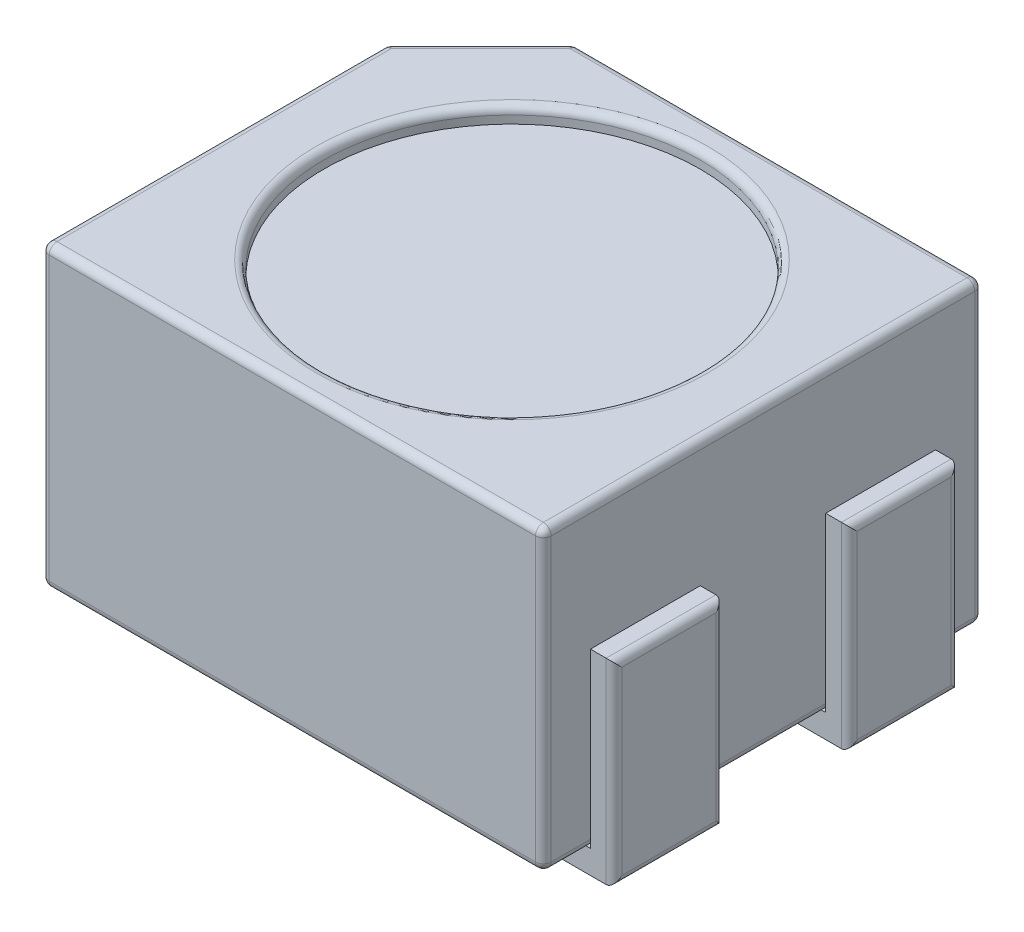
SolidWorks part; units mm, degrees
ref_plane "Спереди" through (0, 0, 0) normal (0, 0, 1) x (1, 0, 0)
ref_plane "Сверху" through (0, 0, 0) normal (0, 1, 0) x (1, 0, 0)
ref_plane "Справа" through (0, 0, 0) normal (1, 0, 0) x (0, 0, -1)
ref_plane "Плоскость1" through (0, 0.15, 0) normal (0, 1, 0) x (1, 0, 0)
sketch "Эскиз1" plane through (0, 0.15, 0) normal (0, 1, 0) x (1, 0, 0)
  line L1 (-1.6, -1.4) -> (1.6, -1.4)
  line L2 (-1.6, -1.4) -> (-1.6, 1.4)
  line L3 (-1.6, 1.4) -> (1.6, 1.4)
  line L4 (1.6, -1.4) -> (1.6, 1.4)
  line L5 (-1.6, -1.4) -> (1.6, 1.4) construction
  line L6 (-1.6, 1.4) -> (1.6, -1.4) construction
  point P0 (0, 0)
extrude "Бобышка-Вытянуть1" add sketch "Эскиз1" along normal blind 1.9
sketch "Эскиз2" plane through (0, 0, 0) normal (0, 1, 0) x (1, 0, 0)
  line L0 (-1.75, -0.4) -> (-0.85, -0.4)
  line L1 (-1.75, 1.1) -> (-0.85, 1.1)
  line L2 (-1.75, 1.1) -> (-1.75, 0.4)
  line L3 (-1.75, 0.4) -> (-0.85, 0.4)
  line L4 (-0.85, 1.1) -> (-0.85, 0.4)
  line L5 (-1.75, 1.1) -> (-0.85, 0.4) construction
  line L6 (-1.75, 0.4) -> (-0.85, 1.1) construction
  line L7 (-1.75, -0.4) -> (-1.75, -1.1)
  line L8 (-1.75, -1.1) -> (-0.85, -1.1)
  line L9 (-0.85, -0.4) -> (-0.85, -1.1)
  line L10 (-1.75, -0.4) -> (-0.85, -1.1) construction
  line L11 (-1.75, -1.1) -> (-0.85, -0.4) construction
  line L12 (0.85, -0.4) -> (1.75, -0.4)
  line L13 (0.85, -0.4) -> (0.85, -1.1)
  line L14 (0.85, -1.1) -> (1.75, -1.1)
  line L15 (1.75, -0.4) -> (1.75, -1.1)
  line L16 (0.85, -0.4) -> (1.75, -1.1) construction
  line L17 (0.85, -1.1) -> (1.75, -0.4) construction
  line L18 (0.85, 1.1) -> (1.75, 1.1)
  line L19 (0.85, 1.1) -> (0.85, 0.4)
  line L20 (0.85, 0.4) -> (1.75, 0.4)
  line L21 (1.75, 1.1) -> (1.75, 0.4)
  line L22 (0.85, 1.1) -> (1.75, 0.4) construction
  line L23 (0.85, 0.4) -> (1.75, 1.1) construction
  point P0 (-1.3, 0.75)
  point P5 (0, 0)
  point P6 (-1.3, -0.75)
  point P11 (0, 0)
  point P12 (0, 0)
  point P13 (0, 0)
  point P14 (1.3, -0.75)
  point P19 (0, 0)
  point P20 (0, 0)
  point P21 (1.3, 0.75)
  point P26 (0, 0)
extrude "Бобышка-Вытянуть2" add sketch "Эскиз2" along normal blind 0.15 separate body
sketch "Эскиз4" plane through (0, 0.15, 0) normal (0, 1, 0) x (1, 0, 0)
  line L0 (1.6, -1.4) -> (1.6, 1.4) construction
  line L1 (1.75, 1.1) -> (1.6, 1.1)
  line L2 (1.75, 1.1) -> (1.75, 0.4)
  line L3 (1.75, 0.4) -> (1.6, 0.4)
  line L4 (1.6, 1.1) -> (1.6, 0.4)
  line L5 (0.85, 0.4) -> (1.75, 0.4) construction
  line L6 (-1.75, -1.1) -> (-0.85, -1.1) construction
  line L7 (1.75, -0.4) -> (1.6, -0.4)
  line L8 (1.75, -0.4) -> (1.75, -1.1)
  line L9 (1.75, -1.1) -> (1.6, -1.1)
  line L10 (1.6, -0.4) -> (1.6, -1.1)
  line L11 (-1.75, -0.4) -> (-1.6, -0.4)
  line L12 (-1.75, -0.4) -> (-1.75, -1.1)
  line L13 (-1.75, -1.1) -> (-1.6, -1.1)
  line L14 (-1.6, -0.4) -> (-1.6, -1.1)
  line L15 (-1.6, 1.4) -> (-1.6, -1.4) construction
  line L16 (-1.75, 0.4) -> (-0.85, 0.4) construction
  line L17 (-1.75, 1.1) -> (-1.6, 1.1)
  line L18 (-1.75, 1.1) -> (-1.75, 0.4)
  line L19 (-1.75, 0.4) -> (-1.6, 0.4)
  line L20 (-1.6, 1.1) -> (-1.6, 0.4)
extrude "Бобышка-Вытянуть3" add sketch "Эскиз4" along normal blind 1.1 separate body
combine bodies "Соединить1" operation type add bodies to combine 110 107
combine bodies "Соединить2" operation type add bodies to combine 108 104
combine bodies "Соединить3" operation type add bodies to combine 109 106
combine bodies "Соединить4" operation type add bodies to combine 111 105
sketch "Эскиз5" plane through (0, 2.05, 0) normal (0, 1, 0) x (1, 0, 0)
  circle A0 centre (0, 0) radius 1.2
extrude "Бобышка-Вытянуть4" add sketch "Эскиз5" against normal blind 1.1 from offset 0.1 separate body
combine bodies "Соединить5" operation type subtract main body 103 bodies to subtract 116
extrude "Бобышка-Вытянуть5" add sketch "Эскиз5<2>" against normal blind 0.9 from offset 0.1 separate body contours A0 offset against normal yes
sketch "Эскиз5<2>" plane through (0, 2.05, 0) normal (0, 1, 0) x (1, 0, 0) same geometry as "Эскиз5"
sketch "Эскиз7" plane through (0, 2.05, 0) normal (0, 1, 0) x (1, 0, 0)
  line L0 (-1.6, 1.4) -> (-1, 1.4)
  line L1 (1.6, 1.4) -> (-1.6, 1.4) construction
  line L2 (-1.6, 1.4) -> (-1.6, 0.8)
  line L3 (-1.6, 1.4) -> (-1.6, -1.4) construction
  line L4 (-1.6, 0.8) -> (-1, 1.4)
  point P5 (0, 0)
extrude "Бобышка-Вытянуть6" add sketch "Эскиз7" against normal blind 0.6 separate body
combine bodies "Соединить6" operation type subtract main body 117 bodies to subtract 119
fillet "Скругление1" radius 0.05 19 edges at (0, 0.15, -1.4) (-1, 1.75, -1.4) (1.6, 1.1, -1.4) (1.6, 0.15, 0) (1.6, 1.1, 1.4) (0, 0.15, 1.4) (-1.6, 1.1, 1.4) (-1.6, 0.15, 0) (-1.6, 0.8, -1.4) (-1.6, 1.75, -0.8) (-1.3, 1.45, -1.4) (-1.3, 1.45, -1.1) (-1.6, 1.45, -1.1) (1.6, 2.05, 0) (0, 2.05, 1.4) (-1.6, 2.05, 0.3) (-1.3, 2.05, -1.1) (0.3, 2.05, -1.4) (0, 2.05, -1.2)
fillet "Скругление2" radius 0.05 4 edges at (-1.75, 1.25, -0.75) (-1.75, 0.625, -0.4) (-1.75, 0, -0.75) (-1.75, 0.625, -1.1)
fillet "Скругление3" radius 0.05 4 edges at (-1.75, 1.25, 0.75) (-1.75, 0.625, 1.1) (-1.75, 0, 0.75) (-1.75, 0.625, 0.4)
fillet "Скругление4" radius 0.05 4 edges at (1.75, 1.25, -0.75) (1.75, 0.625, -1.1) (1.75, 0, -0.75) (1.75, 0.625, -0.4)
fillet "Скругление5" radius 0.05 4 edges at (1.75, 1.25, 0.75) (1.75, 0.625, 0.4) (1.75, 0, 0.75) (1.75, 0.625, 1.1)
